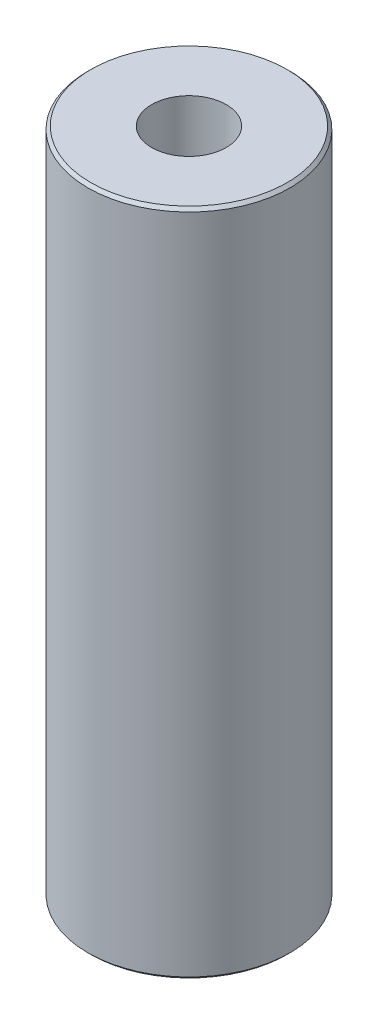
SolidWorks part; units mm, degrees
ref_plane "Front Plane" through (0, 0, 0) normal (0, 0, 1) x (1, 0, 0)
ref_plane "Top Plane" through (0, 0, 0) normal (0, 1, 0) x (1, 0, 0)
ref_plane "Right Plane" through (0, 0, 0) normal (1, 0, 0) x (0, 0, -1)
sketch "Sketch1" plane through (0, 0, 0) normal (0, 1, 0) x (1, 0, 0)
  circle A0 centre (0, 0) radius 60
  dimension "SHAFT_OD" = 120
extrude "Boss-Extrude1" add sketch "Sketch1" along normal blind 396.7765
sketch "Sketch2" plane through (0, 0, 0) normal (0, 1, 0) x (1, 0, 0)
  circle A0 centre (0, 0) radius 22.1153
  dimension "BORE_D" = 44.2306
extrude "Cut-Extrude1" cut sketch "Sketch2" along normal through all
chamfer "Chamfer1" distance 1.7815 angle 45 2 edges at (0, 396.7765, 60) (0, 0, 60)
